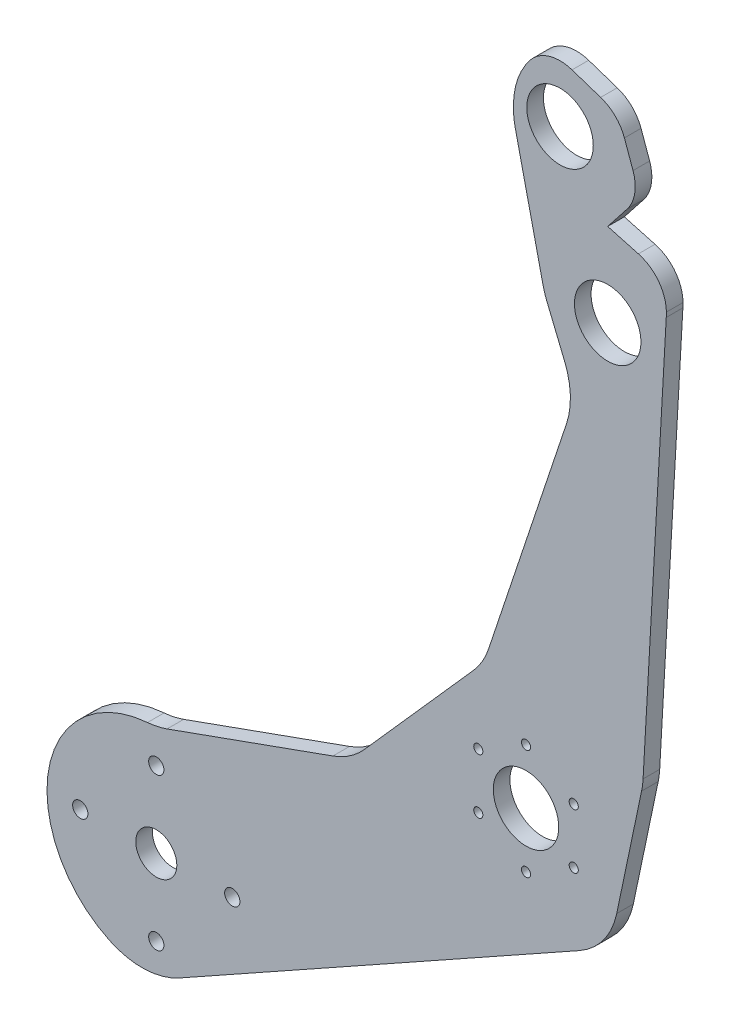
SolidWorks part; units mm, degrees
ref_plane "Front Plane" through (0, 0, 0) normal (0, 0, 1) x (1, 0, 0)
ref_plane "Top Plane" through (0, 0, 0) normal (0, 1, 0) x (1, 0, 0)
ref_plane "Right Plane" through (0, 0, 0) normal (1, 0, 0) x (0, 0, -1)
sketch "Sketch1" plane through (0, 0, 0) normal (0, 0, 1) x (1, 0, 0)
  line L0 (199.796, 71.0781) -> (188.9649, 57.2856)
  line L1 (38.107, -163.0696) -> (103.2618, -139.7016)
  line L2 (103.2618, -139.7016) -> (147.5504, -89.7457)
  line L3 (147.5504, -89.7457) -> (171.8362, -16.8147)
  line L4 (171.8362, -16.8147) -> (178.1894, 2.2642)
  line L5 (178.1894, 2.2642) -> (167.83, 27.4472)
  line L6 (157.4706, 73.0101) -> (157.4706, 93.39)
  line L7 (157.4706, 93.39) -> (170.6001, 98.791)
  line L8 (170.6001, 98.791) -> (192.4684, 91.509)
  line L9 (192.4684, 91.509) -> (199.796, 71.0781)
  line L10 (208.8308, 45.8872) -> (200.6841, -98.6168)
  line L11 (200.6841, -98.6168) -> (189.6112, -151.3856)
  line L12 (189.6112, -151.3856) -> (38.107, -236.12)
  line L13 (188.9649, 57.2856) -> (206.4568, 52.5065)
  line L14 (206.4568, 52.5065) -> (208.8308, 45.8872)
  line L15 (157.4706, 73.0101) -> (167.83, 27.4472)
  line L16 (200.3291, 52.5254) -> (188.9649, 57.2856) construction
  arc A9 (38.107, -163.0696) -> (38.107, -236.12) centre (38.107, -199.5948) ccw
  circle A10 centre (38.107, -199.5948) radius 6.8612
  circle A11 centre (161.6717, -124.7706) radius 10.9347
  circle A12 centre (188.9649, 29.3961) radius 11.1125
  circle A13 centre (173.036, 78.2376) radius 11.1125
  circle A14 centre (38.107, -174.1948) radius 2.5527
  circle A15 centre (63.507, -199.5948) radius 2.5527
  circle A16 centre (38.107, -224.9948) radius 2.5527
  circle A17 centre (12.707, -199.5948) radius 2.5527
  circle A18 centre (161.6717, -106.3556) radius 1.524
  circle A20 centre (177.6196, -115.5631) radius 1.524
  circle A21 centre (177.6196, -133.9781) radius 1.524
  circle A22 centre (161.6717, -143.1856) radius 1.524
  circle A23 centre (145.7239, -133.9781) radius 1.524
  circle A24 centre (145.7239, -115.5631) radius 1.524
  point P33 (38.107, -199.5948)
  point P34 (162.0182, -106.1758)
  point P44 (189.6112, 26.4494)
  point P45 (176.3649, -113.9114)
  point P46 (178.1894, -115.7428)
  point P48 (177.6575, -135.0345)
  point P50 (161.4879, -144.4436)
  point P52 (144.79, -135.306)
  point P53 (188.9649, 29.3961)
  point P54 (144.79, -115.2896)
  point P55 (188.9649, 57.2856)
  point P58 (204.9633, 52.9145)
  point P59 (199.796, 71.0781)
  dimension "D1" = 22.225
  dimension "D2" = 22.225
  dimension "D3" = 4
  dimension "D4" = 25.4
  dimension "D5" = 73.0504
  dimension "D6" = 21.8694
  dimension "D7" = 3.048
  dimension "D8" = 18.415
extrude "Boss-Extrude1" add sketch "Sketch1" along normal blind 5.5562
fillet "Fillet1" radius 25.4 11 edges at (157.4706, 93.39, 2.7781) (157.4706, 73.0101, 2.7781) (167.83, 27.4472, 2.7781) (178.1894, 2.2642, 2.7781) (147.5504, -89.7457, 2.7781) (103.2618, -139.7016, 2.7781) (38.107, -163.0696, 2.7781) (38.107, -236.12, 2.7781) (189.6112, -151.3856, 2.7781) (200.6841, -98.6168, 2.7781) (208.8308, 45.8872, 2.7781)
fillet "Fillet3" radius 12.7 2 edges at (192.4684, 91.509, 2.7781) (170.6001, 98.791, 2.7781)
fillet "Fillet4" radius 12.7 2 edges at (206.4568, 52.5065, 2.7781) (199.796, 71.0781, 2.7781)
